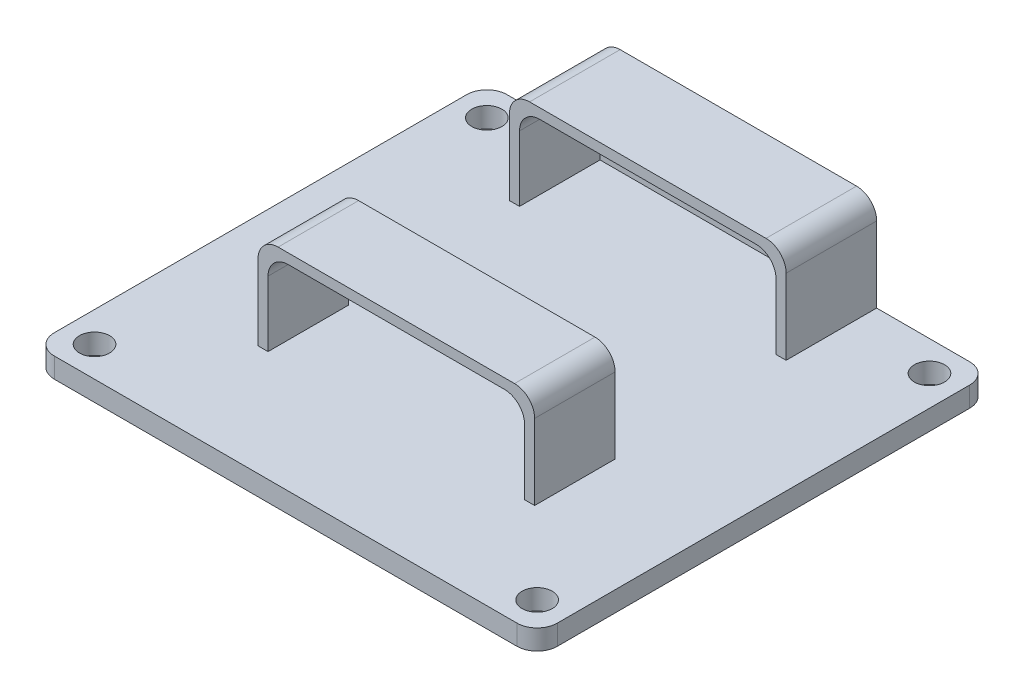
SolidWorks part; units mm, degrees
ref_plane "前视基准面" through (0, 0, 0) normal (0, 0, 1) x (1, 0, 0)
ref_plane "上视基准面" through (0, 0, 0) normal (0, 1, 0) x (1, 0, 0)
ref_plane "右视基准面" through (0, 0, 0) normal (1, 0, 0) x (0, 0, -1)
sketch "草图1" plane through (0, 0, 0) normal (0, 1, 0) x (1, 0, 0)
  line L1 (-23, -22.5) -> (23, -22.5)
  line L2 (-25, -20.5) -> (-25, 20.5)
  line L3 (-23, 22.5) -> (23, 22.5)
  line L4 (25, -20.5) -> (25, 20.5)
  line L5 (-25, -22.5) -> (25, 22.5) construction
  line L6 (-25, 22.5) -> (25, -22.5) construction
  arc A0 (23, 22.5) -> (25, 20.5) centre (23, 20.5) cw
  arc A1 (25, -20.5) -> (23, -22.5) centre (23, -20.5) cw
  arc A2 (-23, -22.5) -> (-25, -20.5) centre (-23, -20.5) cw
  arc A3 (-25, 20.5) -> (-23, 22.5) centre (-23, 20.5) cw
  point P0 (0, 0)
  dimension "D3" = 2
  dimension "D1" = 45
  dimension "D2" = 50
extrude "凸台-拉伸1" add sketch "草图1" along normal blind 2
sketch "草图4" plane through (0, 0, 0) normal (0, 1, 0) x (1, 0, 0)
  line L1 (-22, -19.5) -> (22, -19.5) construction
  line L2 (-22, -19.5) -> (-22, 19.5) construction
  line L3 (-22, 19.5) -> (22, 19.5) construction
  line L4 (22, -19.5) -> (22, 19.5) construction
  line L5 (-22, -19.5) -> (22, 19.5) construction
  line L6 (-22, 19.5) -> (22, -19.5) construction
  circle A0 centre (22, 19.5) radius 1.5
  circle A1 centre (-22, 19.5) radius 1.5
  circle A2 centre (-22, -19.5) radius 1.5
  circle A3 centre (22, -19.5) radius 1.5
  point P0 (0, 0)
  dimension "D3" = 3
  dimension "D4" = 3
  dimension "D5" = 3
  dimension "D6" = 3
  dimension "D1" = 39
  dimension "D2" = 44
extrude "切除-拉伸1" cut sketch "草图4" along normal through all
sketch "草图5" plane through (0, 2, 0) normal (0, 1, 0) x (1, 0, 0)
  line L0 (0, 22.5) -> (0, -22.5) construction
  line L1 (-12.75, -22.5) -> (12.75, -22.5) construction
  line L2 (-12.75, -22.5) -> (-12.75, 22.5) construction
  line L3 (-12.75, 22.5) -> (12.75, 22.5) construction
  line L4 (12.75, -22.5) -> (12.75, 22.5) construction
  line L5 (-12.75, -22.5) -> (12.75, 22.5) construction
  line L6 (-12.75, 22.5) -> (12.75, -22.5) construction
  line L7 (23, 22.5) -> (-23, 22.5) construction
  line L12 (-13.75, 13.5) -> (13.75, 13.5)
  line L13 (-13.75, 13.5) -> (-13.75, 22.5)
  line L23 (-13.75, -11.5) -> (13.75, -11.5)
  line L24 (-13.75, 22.5) -> (13.75, 22.5)
  line L25 (13.75, 13.5) -> (13.75, 22.5)
  line L26 (-13.75, 13.5) -> (13.75, 22.5) construction
  line L27 (-13.75, 22.5) -> (13.75, 13.5) construction
  line L28 (-13.75, -11.5) -> (-13.75, -3.5)
  line L29 (-13.75, -3.5) -> (13.75, -3.5)
  line L30 (13.75, -11.5) -> (13.75, -3.5)
  line L31 (-13.75, -11.5) -> (13.75, -3.5) construction
  line L32 (-13.75, -3.5) -> (13.75, -11.5) construction
  point P0 (0, 0)
  point P8 (0, 18)
  point P9 (0, -7.5)
  dimension "D1" = 45
  dimension "D2" = 25.5
  dimension "D3" = 9
  dimension "D4" = 8
  dimension "D5" = 27.5
  dimension "D6" = 27.5
  dimension "D7" = 30
extrude "凸台-拉伸2" add sketch "草图5" along normal blind 9.5
sketch "草图6" plane through (0, 0, 11.5) normal (0, 0, 1) x (1, 0, 0)
  line L0 (-13.75, 2) -> (13.75, 2) construction
  line L1 (12.75, 10.5) -> (-12.75, 10.5)
  line L2 (12.75, 10.5) -> (12.75, 2)
  line L3 (12.75, 2) -> (-12.75, 2)
  line L4 (-12.75, 10.5) -> (-12.75, 2)
  line L5 (12.75, 10.5) -> (-12.75, 2) construction
  line L6 (12.75, 2) -> (-12.75, 10.5) construction
  line L7 (0, 0) -> (0, 19.9669) construction
  point P0 (0, 6.25)
  point P10 (0, 6.0129)
  point P11 (0, 0)
  dimension "D1" = 25.5
  dimension "D2" = 8.5
extrude "切除-拉伸2" cut sketch "草图6" against normal offset from surface (33 mm away) 1 up to face at (0, 3.875, -22.5)
fillet "圆角1" radius 2 8 edges at (12.75, 10.5, -17.5) (12.75, 10.5, 7.5) (13.75, 11.5, 7.5) (13.75, 11.5, -18) (-12.75, 10.5, 7.5) (-12.75, 10.5, -17.5) (-13.75, 11.5, 7.5) (-13.75, 11.5, -18)
